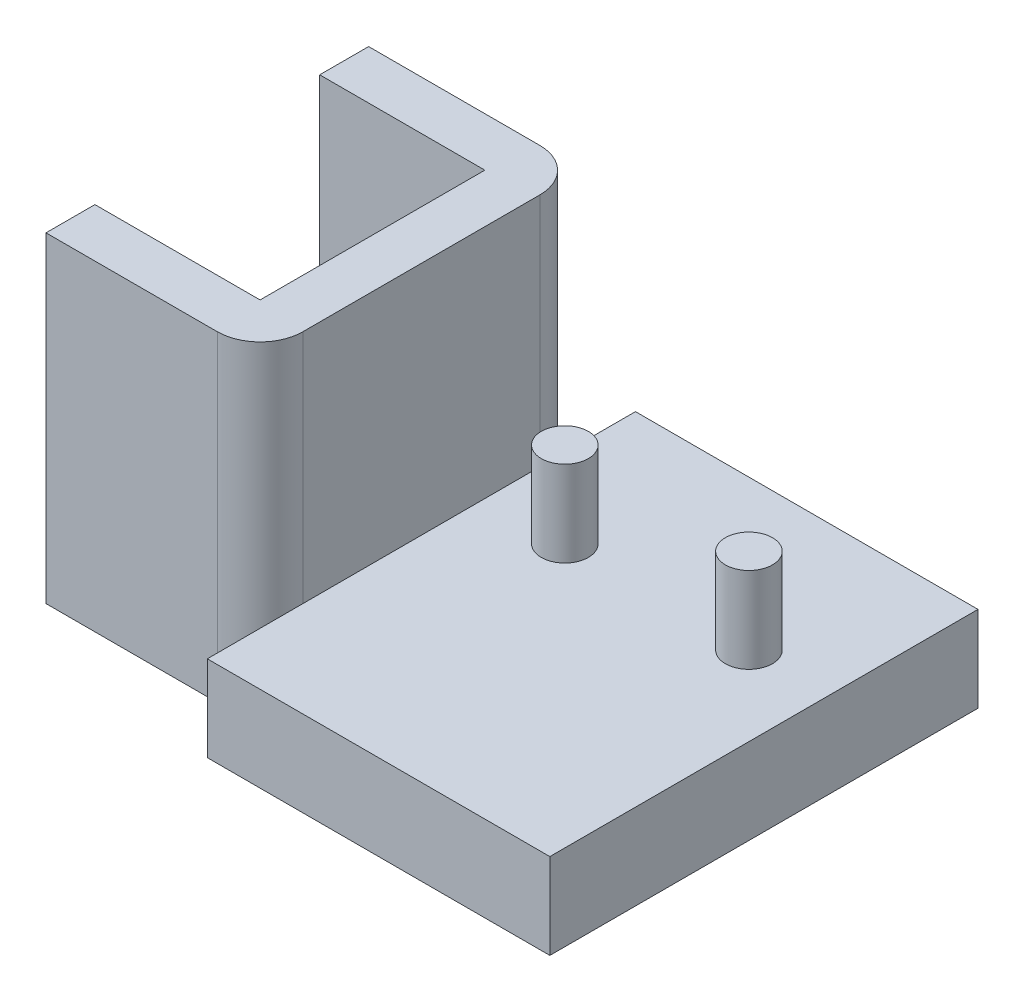
SolidWorks part; units mm, degrees
ref_plane "前视基准面" through (0, 0, 0) normal (0, 0, 1) x (1, 0, 0)
ref_plane "上视基准面" through (0, 0, 0) normal (0, 1, 0) x (1, 0, 0)
ref_plane "右视基准面" through (0, 0, 0) normal (1, 0, 0) x (0, 0, -1)
sketch "草图3" plane through (0, 0, 0) normal (0, 1, 0) x (1, 0, 0)
  line L0 (-6.3835, 11.8607) -> (-6.3835, -3.2093)
  line L1 (-6.3835, -3.2093) -> (1.6165, -3.2093)
  line L2 (3.6165, -1.2093) -> (3.6165, 9.8607)
  line L3 (1.6165, 11.8607) -> (-6.3835, 11.8607)
  line L4 (3.6165, 14.3257) -> (3.6165, -5.6743)
  line L5 (3.6165, -5.6743) -> (19.6165, -5.6743)
  line L6 (19.6165, -5.6743) -> (19.6165, 14.3257)
  line L7 (19.6165, 14.3257) -> (3.6165, 14.3257)
  line L8 (-6.3835, 9.5757) -> (1.3315, 9.5757)
  line L9 (1.3315, 9.5757) -> (1.3315, -0.9243)
  line L10 (1.3315, -0.9243) -> (-6.3835, -0.9243)
  line L11 (-6.3835, -0.9243) -> (-6.3835, 9.5757)
  arc A0 (1.6165, -3.2093) -> (3.6165, -1.2093) centre (1.6165, -1.2093) ccw
  arc A1 (3.6165, 9.8607) -> (1.6165, 11.8607) centre (1.6165, 9.8607) ccw
  dimension "D1" = 2
  dimension "D2" = 16
  dimension "D3" = 20
  dimension "D4" = 2.465
  dimension "D5" = 15.07
  dimension "D6" = 8
  dimension "D7" = 2.285
  dimension "D8" = 2.285
  dimension "D9" = 2.285
extrude "凸台-拉伸3" add sketch "草图3" along normal blind 15 contours L2 A1 L3 L0 L1 A0 region at (-2.3835, 0, -11.6798)
extrude "凸台-拉伸4" add sketch "草图3<4>" along normal blind 4 contours L6 L7 L4 L2 L5 region at (11.6165, 0, -4.3257)
sketch "草图3<4>" plane through (0, 0, 0) normal (0, 1, 0) x (1, 0, 0) same geometry as "草图3"
sketch "草图8" plane through (0, 4, 0) normal (0, 1, 0) x (1, 0, 0)
  line L0 (19.6165, 14.3257) -> (3.6165, 14.3257) construction
  line L2 (3.6165, 14.3257) -> (3.6165, 9.8607) construction
  circle A0 centre (7.3165, 7.3257) radius 1.1
  circle A1 centre (15.9165, 7.3257) radius 1.1
  dimension "D1" = 2.2
  dimension "D2" = 2.2
  dimension "D3" = 7
  dimension "D4" = 7
  dimension "D5" = 3.7
  dimension "D6" = 8.6
extrude "凸台-拉伸5" add sketch "草图8" along normal blind 4
